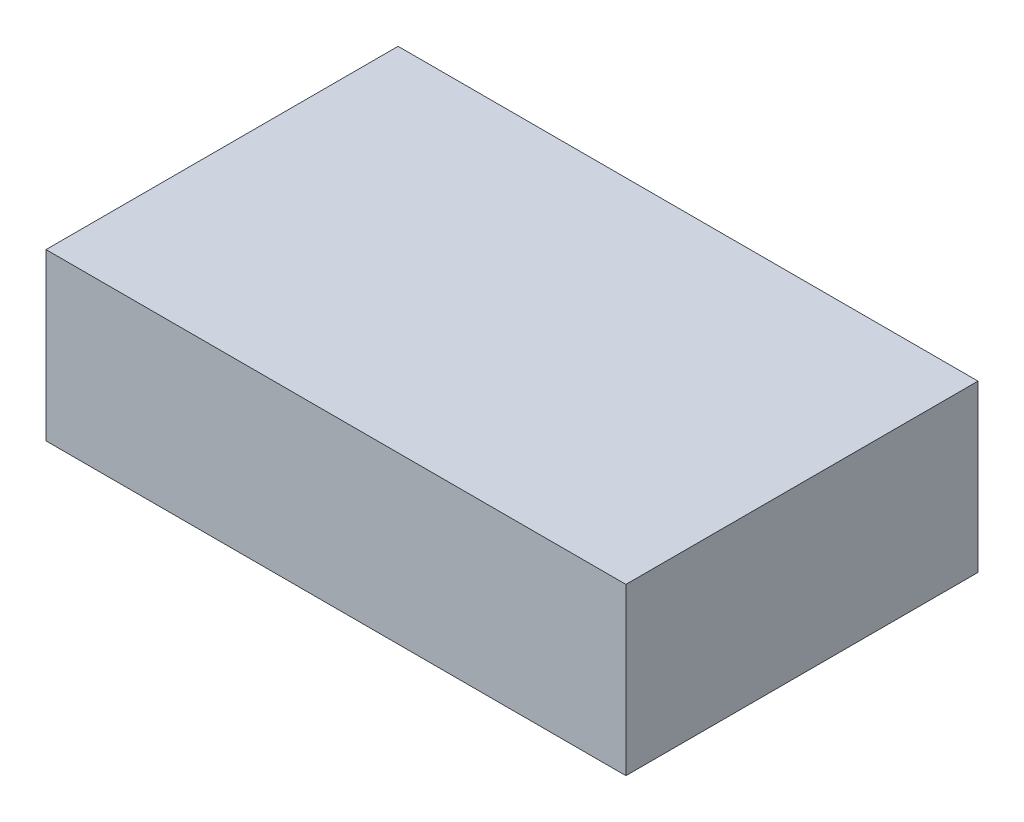
SolidWorks part; units mm, degrees
ref_plane "Front Plane" through (0, 0, 0) normal (0, 0, 1) x (1, 0, 0)
ref_plane "Top Plane" through (0, 0, 0) normal (0, 1, 0) x (1, 0, 0)
ref_plane "Right Plane" through (0, 0, 0) normal (1, 0, 0) x (0, 0, -1)
sketch "Sketch1" plane through (0, 0, 0) normal (0, 1, 0) x (1, 0, 0)
  line L1 (0, 0) -> (355.6, 0)
  line L2 (0, 0) -> (0, 215.9)
  line L3 (0, 215.9) -> (355.6, 215.9)
  line L4 (355.6, 0) -> (355.6, 215.9)
  dimension "D1" = 355.6
  dimension "D2" = 215.9
extrude "Boss-Extrude1" add sketch "Sketch1" along normal blind 101.6
